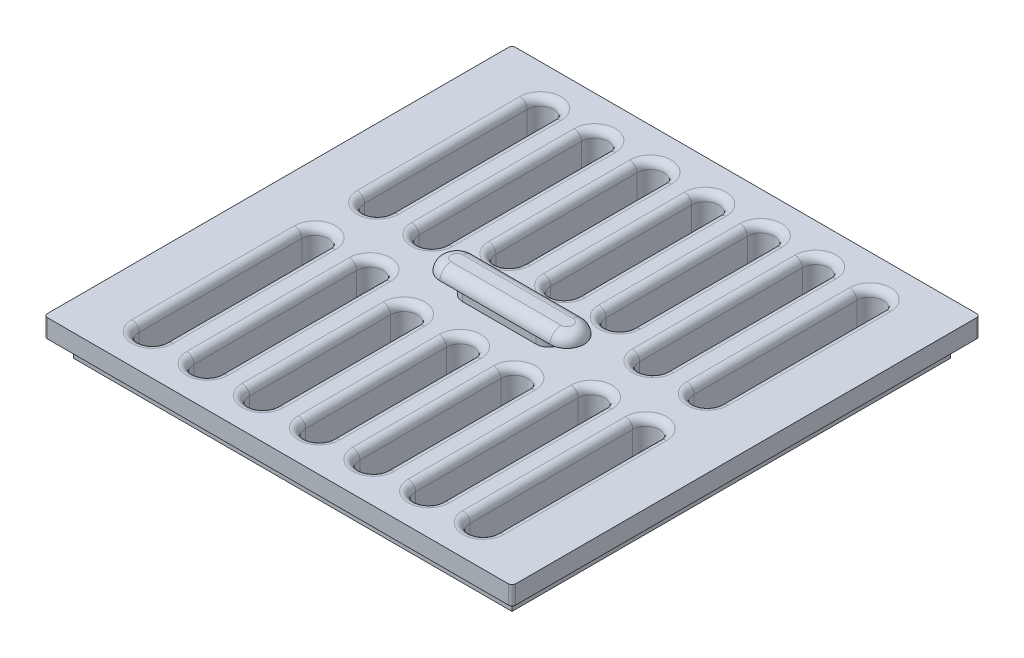
SolidWorks part; units mm, degrees
ref_plane "Front Plane" through (0, 0, 0) normal (0, 0, 1) x (1, 0, 0)
ref_plane "Top Plane" through (0, 0, 0) normal (0, 1, 0) x (1, 0, 0)
ref_plane "Right Plane" through (0, 0, 0) normal (1, 0, 0) x (0, 0, -1)
sketch "Sketch2" plane through (0, 0, 0) normal (0, 1, 0) x (1, 0, 0)
  line L1 (-52.8484, 81.8331) -> (74.1516, 81.8331)
  line L2 (-52.8484, 81.8331) -> (-52.8484, -45.1669)
  line L3 (-52.8484, -45.1669) -> (74.1516, -45.1669)
  line L4 (74.1516, 81.8331) -> (74.1516, -45.1669)
  dimension "D1" = 127
  dimension "D2" = 127
extrude "Boss-Extrude1" add sketch "Sketch2" along normal blind 5
sketch "Sketch3" plane through (0, 0, 0) normal (0, -1, 0) x (1, 0, 0)
  line L0 (74.1516, 45.1669) -> (74.1516, -81.8331) construction
  line L1 (-48.8484, 41.1669) -> (70.1516, 41.1669)
  line L2 (-48.8484, 41.1669) -> (-48.8484, -77.8331)
  line L3 (-48.8484, -77.8331) -> (70.1516, -77.8331)
  line L4 (70.1516, 41.1669) -> (70.1516, -77.8331)
  line L6 (74.1516, -81.8331) -> (-52.8484, -81.8331) construction
  dimension "D1" = 119
  dimension "D2" = 4
  dimension "D3" = 119
  dimension "D4" = 4
extrude "Boss-Extrude2" add sketch "Sketch3" along normal blind 5
fillet "Fillet1" radius 1 4 edges at (74.1516, 2.5, 45.1669) (-52.8484, 2.5, 45.1669) (74.1516, 2.5, -81.8331) (-52.8484, 2.5, -81.8331)
sketch "Sketch4" plane through (0, 5, 0) normal (0, 1, 0) x (1, 0, 0)
  line L8 (0.6516, 18.3331) -> (20.6516, 18.3331) construction
  line L9 (0.6516, 21.7669) -> (20.6516, 21.7669)
  line L10 (0.6516, 14.8992) -> (20.6516, 14.8992)
  arc A0 (0.6516, 21.7669) -> (0.6516, 14.8992) centre (0.6516, 18.3331) ccw
  arc A1 (20.6516, 14.8992) -> (20.6516, 21.7669) centre (20.6516, 18.3331) ccw
  point P14 (10.6516, 18.3331)
extrude "Boss-Extrude3" add sketch "Sketch4" along normal blind 3
sketch "Sketch5" plane through (0, 8, 0) normal (0, 1, 0) x (1, 0, 0)
  line L3 (-4.2822, 18.3331) -> (25.5855, 18.3331) construction
  line L4 (-4.2822, 22.9389) -> (25.5855, 22.9389)
  line L5 (-4.2822, 13.7273) -> (25.5855, 13.7273)
  arc A2 (-4.2822, 22.9389) -> (-4.2822, 13.7273) centre (-4.2822, 18.3331) ccw
  arc A3 (25.5855, 13.7273) -> (25.5855, 22.9389) centre (25.5855, 18.3331) ccw
  point P8 (10.6516, 18.3331)
extrude "Boss-Extrude4" add sketch "Sketch5" along normal blind 3
fillet "Fillet2" radius 3 4 edges at (-8.888, 11, -18.3331) (10.6516, 11, -22.9389) (30.1913, 11, -18.3331) (10.6516, 11, -13.7273)
sketch "Sketch6" plane through (0, 5, 0) normal (0, 1, 0) x (1, 0, 0)
  line L0 (10.6516, 16.7273) -> (10.6516, 80.916) construction
  line L2 (-4.2822, 22.9389) -> (-4.2822, 70.1524) construction
  line L3 (25.5855, 19.9389) -> (25.5855, 41.4497) construction
  line L4 (-4.2822, 13.6349) -> (-38.6839, 13.6349) construction
  line L5 (40.5155, 65.5612) -> (40.5155, 33.4957) construction
  line L6 (-19.2122, 64.4118) -> (-19.2122, 16.2797) construction
  line L8 (55.4455, 57.1506) -> (55.4455, 76.2497) construction
  line L9 (-34.1422, 57.1506) -> (-34.1422, 73.4462) construction
  line L10 (-41.8231, 70.8343) -> (-20.3571, 70.8343) construction
  line L12 (-41.8231, -27.9385) -> (-16.0368, -27.9385) construction
  line L14 (-4.2822, 22.9596) -> (-49.6537, 22.9596) construction
  line L15 (-34.1422, 70.8343) -> (-34.1422, 26.7167) construction
  line L16 (-30.5476, 70.8343) -> (-30.5476, 26.7167)
  line L17 (-37.7369, 70.8343) -> (-37.7369, 26.7167)
  line L18 (-19.263, 70.7002) -> (-19.263, 26.5826) construction
  line L19 (-15.6684, 70.7002) -> (-15.6684, 26.5826)
  line L20 (-22.8577, 70.7002) -> (-22.8577, 26.5826)
  line L21 (40.3914, 70.9514) -> (40.3914, 26.8338) construction
  line L22 (43.986, 70.9514) -> (43.986, 26.8338)
  line L23 (36.7967, 70.9514) -> (36.7967, 26.8338)
  line L24 (55.4564, 70.6596) -> (55.4564, 26.542) construction
  line L25 (59.0511, 70.6596) -> (59.0511, 26.542)
  line L26 (51.8618, 70.6596) -> (51.8618, 26.542)
  line L27 (-34.3796, 9.9271) -> (-34.3796, -34.1906) construction
  line L28 (-30.785, 9.9271) -> (-30.785, -34.1906)
  line L29 (-37.9743, 9.9271) -> (-37.9743, -34.1906)
  line L30 (-19.4508, 9.8797) -> (-19.4508, -34.2379) construction
  line L31 (-15.8562, 9.8797) -> (-15.8562, -34.2379)
  line L32 (-23.0455, 9.8797) -> (-23.0455, -34.2379)
  line L33 (40.5542, 9.9656) -> (40.5542, -34.1521) construction
  line L34 (44.1488, 9.9656) -> (44.1488, -34.1521)
  line L35 (36.9595, 9.9656) -> (36.9595, -34.1521)
  line L36 (55.3687, 9.9656) -> (55.3687, -34.1521) construction
  line L37 (58.9633, 9.9656) -> (58.9633, -34.1521)
  line L38 (51.774, 9.9656) -> (51.774, -34.1521)
  line L39 (-4.2822, 70.8343) -> (-4.2822, 32.5656) construction
  line L40 (-0.6202, 70.8343) -> (-0.6202, 32.5656)
  line L41 (-7.9442, 70.8343) -> (-7.9442, 32.5656)
  line L42 (10.695, 70.7122) -> (10.695, 32.4435) construction
  line L43 (14.357, 70.7122) -> (14.357, 32.4435)
  line L44 (7.033, 70.7122) -> (7.033, 32.4435)
  line L45 (25.59, 70.8844) -> (25.59, 32.6157) construction
  line L46 (29.252, 70.8844) -> (29.252, 32.6157)
  line L47 (21.928, 70.8844) -> (21.928, 32.6157)
  line L48 (-4.3646, 4.0534) -> (-4.3646, -34.2153) construction
  line L49 (-0.7026, 4.0534) -> (-0.7026, -34.2153)
  line L50 (-8.0266, 4.0534) -> (-8.0266, -34.2153)
  line L51 (10.8473, 4.0534) -> (10.8473, -34.2153) construction
  line L52 (14.5093, 4.0534) -> (14.5093, -34.2153)
  line L53 (7.1853, 4.0534) -> (7.1853, -34.2153)
  line L54 (25.5972, 4.0534) -> (25.5972, -34.2153) construction
  line L55 (29.2592, 4.0534) -> (29.2592, -34.2153)
  line L56 (21.9352, 4.0534) -> (21.9352, -34.2153)
  arc A0 (-30.5476, 70.8343) -> (-37.7369, 70.8343) centre (-34.1422, 70.8343) ccw
  arc A1 (-37.7369, 26.7167) -> (-30.5476, 26.7167) centre (-34.1422, 26.7167) ccw
  arc A2 (-15.6684, 70.7002) -> (-22.8577, 70.7002) centre (-19.263, 70.7002) ccw
  arc A3 (-22.8577, 26.5826) -> (-15.6684, 26.5826) centre (-19.263, 26.5826) ccw
  arc A4 (43.986, 70.9514) -> (36.7967, 70.9514) centre (40.3914, 70.9514) ccw
  arc A5 (36.7967, 26.8338) -> (43.986, 26.8338) centre (40.3914, 26.8338) ccw
  arc A6 (59.0511, 70.6596) -> (51.8618, 70.6596) centre (55.4564, 70.6596) ccw
  arc A7 (51.8618, 26.542) -> (59.0511, 26.542) centre (55.4564, 26.542) ccw
  arc A8 (-30.785, 9.9271) -> (-37.9743, 9.9271) centre (-34.3796, 9.9271) ccw
  arc A9 (-37.9743, -34.1906) -> (-30.785, -34.1906) centre (-34.3796, -34.1906) ccw
  arc A10 (-15.8562, 9.8797) -> (-23.0455, 9.8797) centre (-19.4508, 9.8797) ccw
  arc A11 (-23.0455, -34.2379) -> (-15.8562, -34.2379) centre (-19.4508, -34.2379) ccw
  arc A12 (44.1488, 9.9656) -> (36.9595, 9.9656) centre (40.5542, 9.9656) ccw
  arc A13 (36.9595, -34.1521) -> (44.1488, -34.1521) centre (40.5542, -34.1521) ccw
  arc A14 (58.9633, 9.9656) -> (51.774, 9.9656) centre (55.3687, 9.9656) ccw
  arc A15 (51.774, -34.1521) -> (58.9633, -34.1521) centre (55.3687, -34.1521) ccw
  arc A16 (-0.6202, 70.8343) -> (-7.9442, 70.8343) centre (-4.2822, 70.8343) ccw
  arc A17 (-7.9442, 32.5656) -> (-0.6202, 32.5656) centre (-4.2822, 32.5656) ccw
  arc A18 (14.357, 70.7122) -> (7.033, 70.7122) centre (10.695, 70.7122) ccw
  arc A19 (7.033, 32.4435) -> (14.357, 32.4435) centre (10.695, 32.4435) ccw
  arc A20 (29.252, 70.8844) -> (21.928, 70.8844) centre (25.59, 70.8844) ccw
  arc A21 (21.928, 32.6157) -> (29.252, 32.6157) centre (25.59, 32.6157) ccw
  arc A22 (-0.7026, 4.0534) -> (-8.0266, 4.0534) centre (-4.3646, 4.0534) ccw
  arc A23 (-8.0266, -34.2153) -> (-0.7026, -34.2153) centre (-4.3646, -34.2153) ccw
  arc A24 (14.5093, 4.0534) -> (7.1853, 4.0534) centre (10.8473, 4.0534) ccw
  arc A25 (7.1853, -34.2153) -> (14.5093, -34.2153) centre (10.8473, -34.2153) ccw
  arc A26 (29.2592, 4.0534) -> (21.9352, 4.0534) centre (25.5972, 4.0534) ccw
  arc A27 (21.9352, -34.2153) -> (29.2592, -34.2153) centre (25.5972, -34.2153) ccw
  point P27 (-34.1422, 48.7755)
  point P34 (-19.263, 48.6414)
  point P41 (40.3914, 48.8926)
  point P48 (55.4564, 48.6008)
  point P55 (-34.3796, -12.1317)
  point P62 (-19.4508, -12.1791)
  point P69 (40.5542, -12.0932)
  point P76 (55.3687, -12.0932)
  point P83 (-4.2822, 51.6999)
  point P90 (10.695, 51.5778)
  point P97 (25.59, 51.75)
  point P104 (-4.3646, -15.081)
  point P111 (10.8473, -15.081)
  point P118 (25.5972, -15.081)
extrude "Cut-Extrude1" cut sketch "Sketch6" against normal blind 23
fillet "Fillet3" radius 2 56 edges at (55.4564, 5, -22.9473) (51.8618, 5, -48.6008) (55.4564, 5, -74.2543) (40.3914, 5, -23.2392) (36.7967, 5, -48.8926) (40.3914, 5, -74.5461) (25.59, 5, -28.9537) (21.928, 5, -51.75) (25.59, 5, -74.5464) (10.695, 5, -28.7815) (7.033, 5, -51.5778) (10.695, 5, -74.3742) (-4.2822, 5, -28.9036) (-7.9442, 5, -51.6999) (-4.2822, 5, -74.4963) (-19.263, 5, -22.9879) (-22.8577, 5, -48.6414) (-19.263, 5, -74.2949) (-34.1422, 5, -23.122) (-37.7369, 5, -48.7755) (-34.1422, 5, -74.4289) (-34.3796, 5, 37.7852) (-37.9743, 5, 12.1317) (-34.3796, 5, -13.5217) (-19.4508, 5, 37.8325) (-23.0455, 5, 12.1791) (-19.4508, 5, -13.4744) (-4.3646, 5, 37.8773) (-8.0266, 5, 15.081) (-4.3646, 5, -7.7154) (10.8473, 5, 37.8773) (7.1853, 5, 15.081) (10.8473, 5, -7.7154) (25.5972, 5, 37.8773) (21.9352, 5, 15.081) (25.5972, 5, -7.7154) (40.5542, 5, 37.7467) (36.9595, 5, 12.0932) (40.5542, 5, -13.5602) (55.3687, 5, 37.7467) (51.774, 5, 12.0932) (55.3687, 5, -13.5602) (59.0511, 5, -48.6008) (43.986, 5, -48.8926) (29.252, 5, -51.75) (14.357, 5, -51.5778) (-0.6202, 5, -51.6999) (-15.6684, 5, -48.6414) (-30.5476, 5, -48.7755) (-30.785, 5, 12.1317) (-15.8562, 5, 12.1791) (-0.7026, 5, 15.081) (14.5093, 5, 15.081) (29.2592, 5, 15.081) (44.1488, 5, 12.0932) (58.9633, 5, 12.0932)
